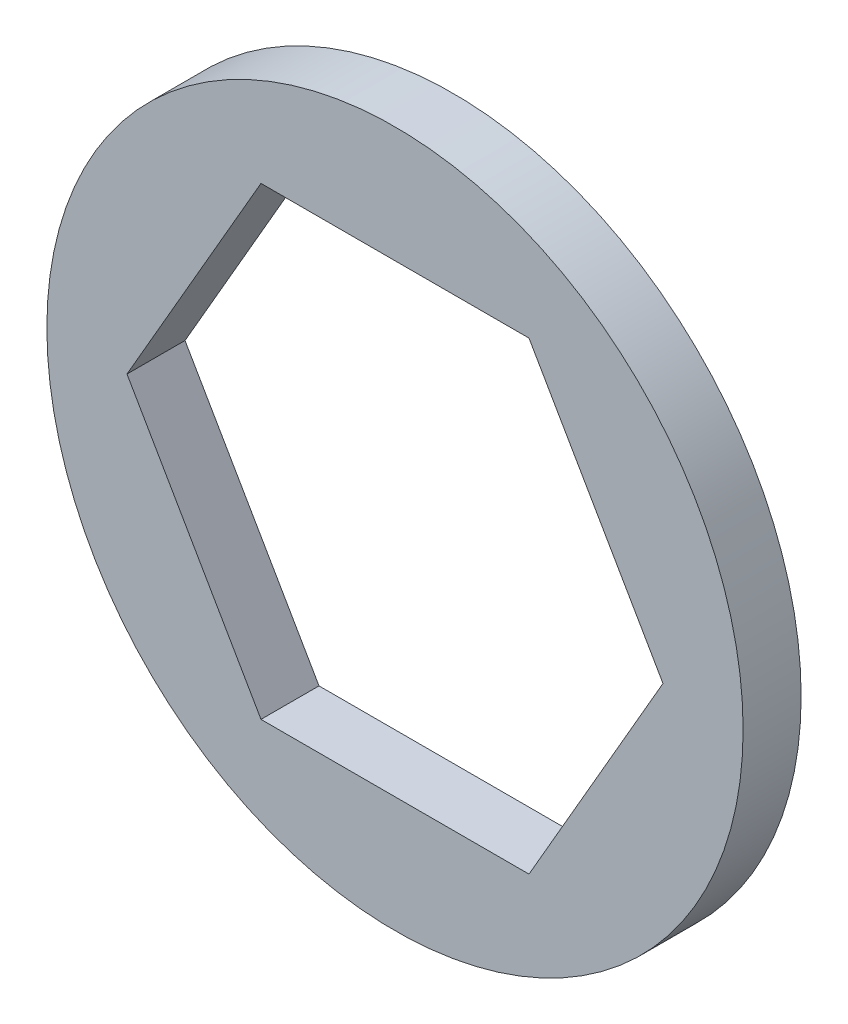
SolidWorks part; units mm, degrees
ref_plane "Front Plane" through (0, 0, 0) normal (0, 0, 1) x (1, 0, 0)
ref_plane "Top Plane" through (0, 0, 0) normal (0, 1, 0) x (1, 0, 0)
ref_plane "Right Plane" through (0, 0, 0) normal (1, 0, 0) x (0, 0, -1)
sketch "Sketch1" plane through (0, 0, 0) normal (0, 0, 1) x (1, 0, 0)
  line L1 (3.6662, 6.35) -> (-3.6662, 6.35)
  line L2 (-3.6662, 6.35) -> (-7.3323, 0)
  line L3 (-7.3323, 0) -> (-3.6662, -6.35)
  line L4 (-3.6662, -6.35) -> (3.6662, -6.35)
  line L5 (3.6662, -6.35) -> (7.3323, 0)
  line L6 (7.3323, 0) -> (3.6662, 6.35)
  circle A0 centre (0, 0) radius 6.35 construction
  circle A1 centre (0, 0) radius 9.525
  point P1 (0, 6.35)
  dimension "D1" = 12.7
  dimension "D2" = 19.05
extrude "Boss-Extrude1" add sketch "Sketch1" along normal blind 1.5875
